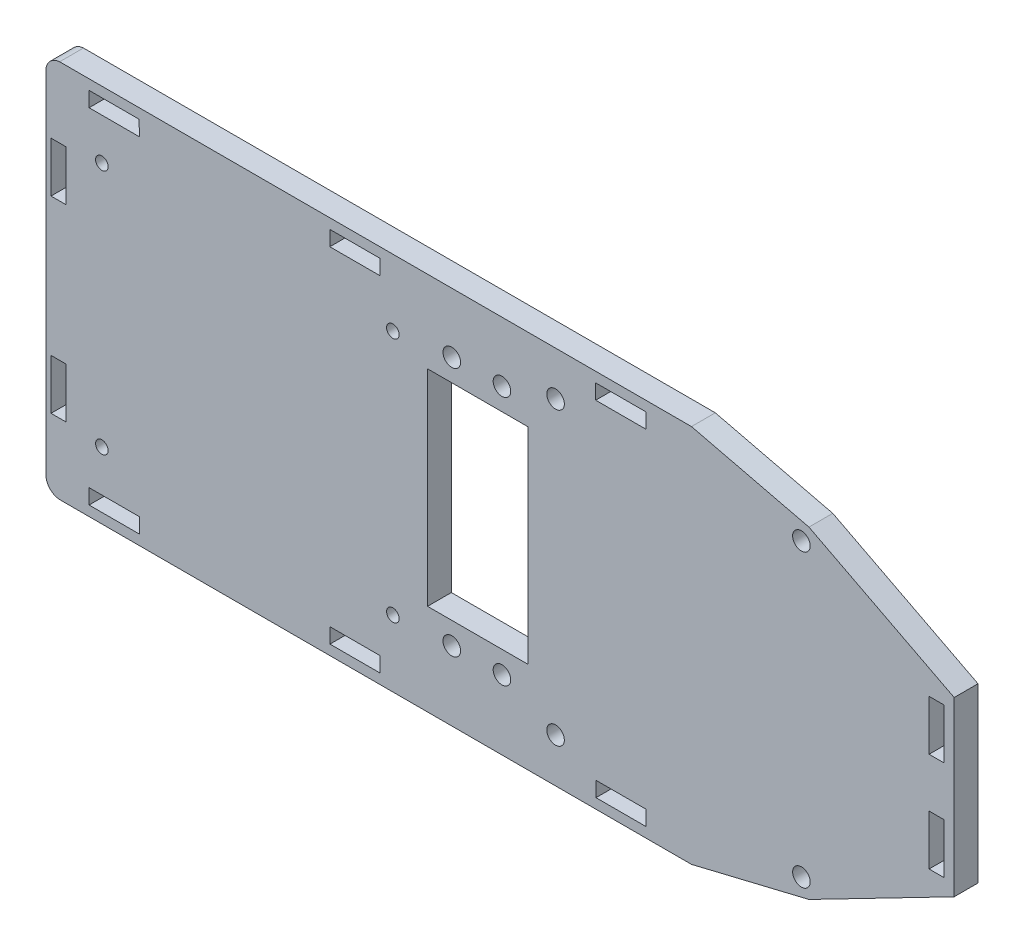
SolidWorks part; units mm, degrees
ref_plane "Front Plane" through (0, 0, 0) normal (0, 0, 1) x (1, 0, 0)
ref_plane "Top Plane" through (0, 0, 0) normal (0, 1, 0) x (1, 0, 0)
ref_plane "Right Plane" through (0, 0, 0) normal (1, 0, 0) x (0, 0, -1)
sketch "Sketch1" plane through (0, 0, 0) normal (0, 0, 1) x (1, 0, 0)
  line L1 (-90.5, -37.785) -> (90.5, -37.785)
  line L2 (-90.5, -37.785) -> (-90.5, 37.785)
  line L3 (-90.5, 37.785) -> (90.5, 37.785)
  line L4 (90.5, -37.785) -> (90.5, 37.785)
  line L5 (-90.5, -37.785) -> (90.5, 37.785) construction
  line L6 (-90.5, 37.785) -> (90.5, -37.785) construction
  point P0 (0, 0)
extrude "Boss-Extrude2" add sketch "Sketch1" along normal blind 4.75
sketch "Sketch6" plane through (0, 0, 4.75) normal (0, 0, 1) x (1, 0, 0)
  line L0 (-90.5, 0) -> (90.5, 0) construction
  line L1 (-90.5, 37.785) -> (-90.5, -37.785) construction
  line L2 (90.5, -37.785) -> (90.5, 37.785) construction
  line L3 (0, 37.785) -> (0, -37.785) construction
  line L4 (90.5, 37.785) -> (-90.5, 37.785) construction
  line L5 (-90.5, -37.785) -> (90.5, -37.785) construction
  line L6 (-90.5, 34.4318) -> (-90.5, -34.4318)
  line L7 (90.5, 17.2) -> (90.5, -17.2)
  line L10 (-21.3732, 40.787) -> (-21.3732, -34.783) construction
  line L11 (-81.9134, 32.786) -> (-71.8797, 32.7858)
  line L12 (-89.5, 23.75) -> (-86.5, 23.75)
  line L13 (-89.5, 23.75) -> (-89.5, 13.75)
  line L14 (-89.5, 13.75) -> (-86.5, 13.75)
  line L15 (-86.5, 23.75) -> (-86.5, 13.75)
  line L16 (-89.5, -13.75) -> (-86.5, -13.75)
  line L17 (-89.5, -13.75) -> (-89.5, -23.75)
  line L18 (-89.5, -23.75) -> (-86.5, -23.75)
  line L19 (-86.5, -13.75) -> (-86.5, -23.75)
  line L20 (-33.9297, 32.785) -> (-33.9309, 35.785)
  line L21 (-33.9297, 32.785) -> (-23.9273, 32.7887)
  line L22 (-33.9309, 35.785) -> (-23.931, 35.785)
  line L23 (-23.9273, 32.7887) -> (-23.931, 35.785)
  line L24 (-71.8797, 32.7858) -> (-71.9473, 35.785)
  line L25 (-81.9134, 32.786) -> (-81.9472, 35.785)
  line L26 (-81.9472, 35.785) -> (-71.9473, 35.785)
  line L27 (-81.9134, -32.785) -> (-71.8797, -32.7852)
  line L28 (-71.9135, -35.785) -> (-71.8797, -32.7852)
  line L29 (-81.9135, -35.785) -> (-71.9135, -35.785)
  line L30 (-81.9135, -35.785) -> (-81.9134, -32.785)
  line L31 (-33.9026, -35.7859) -> (-23.8868, -35.7861)
  line L32 (-33.9026, -35.7859) -> (-33.9037, -32.7859)
  line L33 (-23.8868, -35.7861) -> (-23.8868, -32.7861)
  line L34 (-33.9037, -32.7859) -> (-23.8868, -32.7861)
  line L35 (85.5, 14.9) -> (85.5, 4.9)
  line L36 (88.5, 14.9) -> (88.5, 4.9)
  line L37 (85.5, 4.9) -> (88.5, 4.9)
  line L38 (85.5, 14.9) -> (88.5, 14.9)
  line L40 (29.053, 32.7887) -> (29.053, 35.785)
  line L41 (19.053, 32.7887) -> (29.053, 32.7887)
  line L42 (19.053, 32.7887) -> (19.053, 35.785)
  line L43 (19.053, 35.785) -> (29.053, 35.785)
  line L44 (19.1132, -32.785) -> (29.053, -32.785)
  line L45 (19.1132, -35.785) -> (19.1132, -32.785)
  line L46 (19.1132, -35.785) -> (29.053, -35.785)
  line L47 (29.053, -35.785) -> (29.053, -32.785)
  line L50 (-87.3981, 37.785) -> (38.1419, 37.785)
  line L51 (-14.4594, 21.457) -> (5.5406, 21.457)
  line L52 (-14.4594, 21.457) -> (-14.4594, -19.543)
  line L53 (-14.4594, -19.543) -> (5.5406, -19.543)
  line L54 (5.5406, 21.457) -> (5.5406, -19.543)
  line L58 (-87.3981, -37.785) -> (38.1419, -37.785)
  line L60 (85.5, -14.9) -> (88.5, -14.9)
  line L61 (88.5, -14.9) -> (88.5, -4.9)
  line L62 (85.5, -4.9) -> (88.5, -4.9)
  line L63 (85.5, -14.9) -> (85.5, -4.9)
  line L64 (38.1419, -37.785) -> (61.5528, -32.1352)
  line L65 (61.5528, -32.1352) -> (90.5, -17.2)
  line L66 (38.1419, 37.785) -> (61.5528, 32.14)
  line L67 (61.5528, 32.14) -> (90.5, 17.2)
  arc A0 (-87.3981, 37.785) -> (-90.5, 34.4318) centre (-87.5923, 34.8533) ccw
  arc A1 (-90.5, -34.4318) -> (-87.3981, -37.785) centre (-87.5923, -34.8533) ccw
  circle A8 centre (-9.6294, 25.857) radius 1.75
  circle A9 centre (0.3706, 25.857) radius 1.75
  circle A10 centre (0.3706, -23.943) radius 1.75
  circle A11 centre (-9.6294, -23.943) radius 1.75
  circle A12 centre (11.053, -29) radius 1.75
  circle A13 centre (11.053, 29) radius 1.75
  circle A14 centre (60.053, -29) radius 1.75
  circle A15 centre (60.053, 29) radius 1.75
  circle A16 centre (-79.3732, 24.5) radius 1.25
  circle A17 centre (-79.3732, -24.5) radius 1.25
  circle A18 centre (-21.3732, -24.5) radius 1.25
  circle A19 centre (-21.3732, 24.5) radius 1.25
  point P21 (90.5, 0)
  line M4 (90.5, -37.785) -> (90.5, 37.785)
  line M5 (90.5, 37.785) -> (-90.5, 37.785)
  line M6 (-90.5, 37.785) -> (-90.5, -37.785)
  line M7 (-90.5, -37.785) -> (90.5, -37.785)
  dimension "D1" = 58
  dimension "D3" = 49
  dimension "D2" = 29
  dimension "D4" = 58
  dimension "D10" = 2
  dimension "D11" = 4.4
  dimension "D16" = 32.14
  dimension "D17" = 2
  dimension "D5" = 2
  dimension "D6" = 2
  dimension "D7" = 2
  dimension "D8" = 43
  dimension "D9" = 49.8
  dimension "D12" = 4.4
  dimension "D13" = 58
  dimension "D14" = 49
  dimension "D15" = 24.5
  dimension "D18" = 1
extrude "Cut-Extrude7" cut sketch "Sketch6" against normal blind 9 contours L38 L35 L37 L36 | L43 L42 L41 L40 | A9 | A8 | A11 | A10 | L46 L47 L44 L45 | L21 L23 L22 L20 | L26 L25 L11 L24 | A0 M5 M6 | L15 L12 L13 L14 | L19 L16 L17 L18 | A1 M6 M7 | L30 L29 L28 L27 | A16 | L34 L32 L31 L33 | L65 L64 M7 M4 | L66 L67 M4 M5 | L54 L51 L52 L53 | A17 | A18 | L44 L47 L46 L45 | A10 | L52 L51 L54 L53 | L60 L61 L62 L63 | A12 | A14 | A13 | A15 | A19 region at (-89.8524, 37.1595, 4.75) region at (-89.8524, -37.1595, 4.75) region at (75.0644, 31.3167, 4.75) region at (75.0611, -31.3164, 4.75) region at (-76.9218, 34.2846, 4.75) region at (-88, 18.75, 4.75) region at (-88, -18.75, 4.75) region at (-28.9307, 34.2859, 4.75) region at (-76.9051, -34.2842, 4.75) region at (-28.895, -34.286, 4.75) region at (87, 9.9, 4.75) region at (24.053, 34.2869, 4.75) region at (24.0831, -34.285, 4.75) region at (-4.4594, 0.957, 4.75) region at (-9.6294, 25.857, 4.75) region at (0.3706, 25.857, 4.75) region at (0.3706, -23.943, 4.75) region at (-9.6294, -23.943, 4.75) region at (-79.3732, 24.5, 4.75) region at (-79.3732, -24.5, 4.75) region at (-21.3732, -24.5, 4.75)
